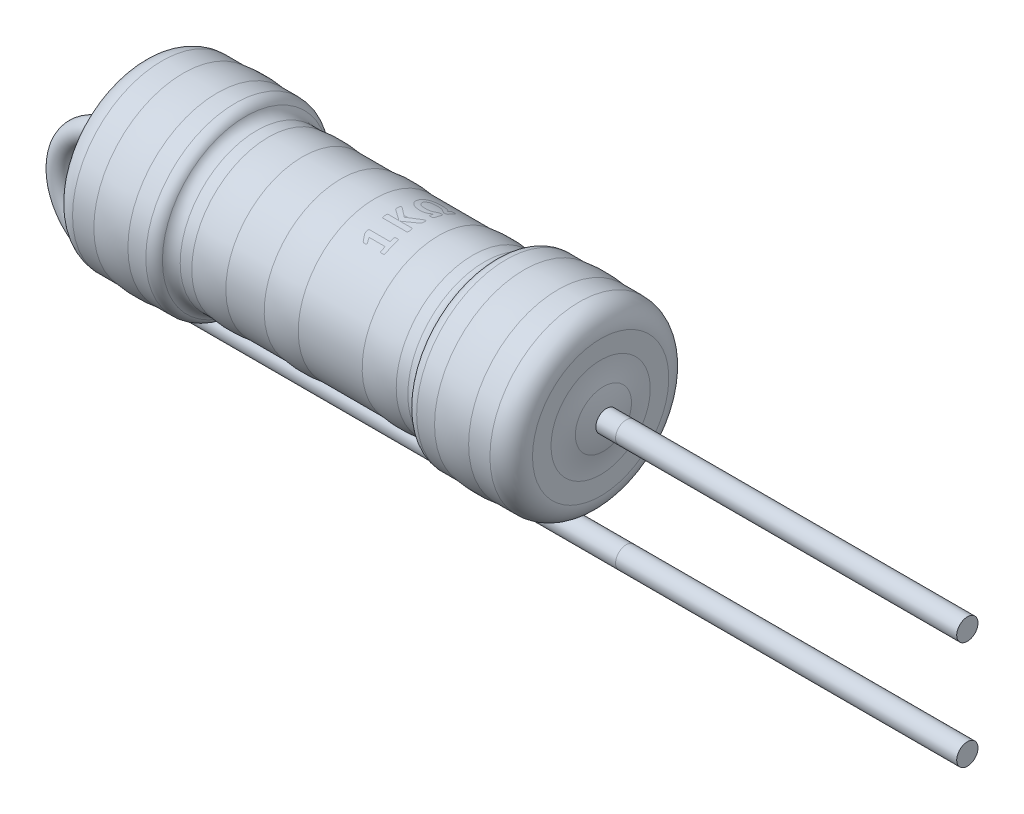
SolidWorks part; units mm, degrees
ref_plane "Front Plane" through (0, 0, 0) normal (0, 0, 1) x (1, 0, 0)
ref_plane "Top Plane" through (0, 0, 0) normal (0, 1, 0) x (1, 0, 0)
ref_plane "Right Plane" through (0, 0, 0) normal (1, 0, 0) x (0, 0, -1)
sketch "Sketch Set Wire Width" plane through (0, 0, 0) normal (0, 0, 1) x (1, 0, 0)
  line L0 (0, 0) -> (6, 0)
  line L1 (6, -2.54) -> (-6, -2.54)
  line L2 (6, 0) -> (14.0102, 0)
  line L3 (-6, 0) -> (-6, -2.54) construction
  line L4 (-6, 0) -> (-6, -2.54) construction
  line L5 (6, -2.54) -> (6, 0) construction
  line L6 (6, -2.54) -> (14.0102, -2.54)
  line L7 (14.0102, -2.54) -> (14.0102, 0) construction
  line L8 (-6, 0) -> (0, 0)
  arc A0 (-6, 0) -> (-6, -2.54) centre (-6, -1.27) ccw
  dimension "D2" = 2.54
  dimension "D3" = 30
  dimension "D1" = 12
  dimension "D4" = 6
sketch "Sketch Wire Diameter" plane through (0, 0, 0) normal (1, 0, 0) x (0, 0, -1)
  circle A0 centre (0, 0) radius 0.25
  dimension "D1" = 0.5
sweep "SET WIRE LENGTH" add profiles "Sketch Wire Diameter" path "Sketch Set Wire Width"
sketch "Sketch3" plane through (0, 0, 0) normal (0, 0, 1) x (1, 0, 0)
  line L0 (-5.4, 0) -> (5.4, 0)
  line L1 (0, 0) -> (0, 1.8) construction
  line L2 (-2.9, 1.8) -> (2.9, 1.8)
  line L3 (-5.4, 0) -> (-5.4, 1.6)
  line L4 (-4.9, 2.1) -> (-3.18, 2.1)
  line L5 (-2.9, 1.82) -> (-2.9, 1.8)
  line L6 (5.4, 0) -> (5.4, 1.6)
  line L7 (4.9, 2.1) -> (3.18, 2.1)
  line L8 (2.9, 1.82) -> (2.9, 1.8)
  arc A0 (-5.4, 1.6) -> (-4.9, 2.1) centre (-4.9, 1.6) cw
  arc A1 (5.4, 1.6) -> (4.9, 2.1) centre (4.9, 1.6) ccw
  arc A2 (-3.18, 2.1) -> (-2.9, 1.82) centre (-3.18, 1.82) cw
  arc A3 (3.18, 2.1) -> (2.9, 1.82) centre (3.18, 1.82) ccw
  dimension "D5" = 0.5
  dimension "D6" = 0.28
  dimension "D1" = 10.8
  dimension "D2" = 5.8
  dimension "D3" = 1.8
  dimension "D4" = 2.1
revolve "Revolve2" add sketch "Sketch3" angle 360 about L0
fillet "Fillet1" radius 0.3 2 edges at (2.9, 0, 1.8) (-2.9, 0, 1.8)
sketch "Sketch5" plane through (0, 0, 0) normal (0, 0, 1) x (1, 0, 0)
  line L0 (0, 0) -> (2, 0) construction
  line L1 (0, 0) -> (-0.3, 0) construction
  line L2 (-0.3, 0) -> (-2, 0) construction
  line L3 (-2, 0) -> (-4, 0) construction
  line L4 (2, 0) -> (4, 0) construction
  line L5 (-4, 0) -> (-4, 2.1) construction
  line L6 (-0.3, 0) -> (-0.3, 1.8) construction
  line L7 (-2, 0) -> (-2, 1.8) construction
  line L8 (2, 0) -> (2, 1.8) construction
  line L9 (4, 0) -> (4, 2.1) construction
  line L10 (-4, 2.1) -> (-4, 2.13) construction
  line L11 (-4.9, 2.1) -> (-3.18, 2.1) construction
  line L12 (4.9, 2.1) -> (3.18, 2.1) construction
  line L13 (-2.9, 1.8) -> (2.9, 1.8) construction
  line L14 (-2, 1.8) -> (-2, 1.83) construction
  line L17 (-4.4, 2.1) -> (-3.6, 2.1)
  line L19 (-5.4, 0) -> (5.4, 0) construction
  line L22 (-2.4, 1.8) -> (-1.6, 1.8) construction
  line L26 (-0.7, 1.8) -> (0.1, 1.8) construction
  line L30 (1.6, 1.8) -> (2.4, 1.8) construction
  line L34 (3.6, 2.1) -> (4.4, 2.1) construction
  line L36 (-0.3, 1.8) -> (-0.3, 1.83) construction
  line L37 (2, 1.8) -> (2, 1.83) construction
  line L38 (4, 2.1) -> (4, 2.13) construction
  arc A0 (-4.4, 2.1) -> (-3.6, 2.1) centre (-4, -0.5517) cw
  arc A1 (-2.4, 1.8) -> (-1.6, 1.8) centre (-2, -0.8517) cw construction
  arc A2 (-0.7, 1.8) -> (0.1, 1.8) centre (-0.3, -0.8517) cw construction
  arc A3 (1.6, 1.8) -> (2.4, 1.8) centre (2, -0.8517) cw construction
  arc A4 (3.6, 2.1) -> (4.4, 2.1) centre (4, -0.5517) cw construction
  dimension "D3" = 0.8
  dimension "D1" = 4
  dimension "D2" = 4
  dimension "D4" = 0.03
  dimension "D5" = 2
  dimension "D6" = 2
  dimension "D7" = 1.7
revolve "Band 1" add sketch "Sketch5" angle 360 about L2
sketch "Sketch8" plane through (0, 0, 0) normal (0, 0, 1) x (1, 0, 0)
  line L0 (-2.4, 1.8) -> (-1.6, 1.8) construction
  line L1 (-2.4, 1.8) -> (-1.6, 1.8)
  arc A0 (-1.6, 1.8) -> (-2.4, 1.8) centre (-2, -0.8517) ccw construction
  arc A1 (-1.6, 1.8) -> (-2.4, 1.8) centre (-2, -0.8517) ccw
revolve "Band 2" add sketch "Sketch8" angle 360 about L2
sketch "Sketch9" plane through (0, 0, 0) normal (0, 0, 1) x (1, 0, 0)
  line L0 (-0.7, 1.8) -> (0.1, 1.8) construction
  line L1 (-0.7, 1.8) -> (0.1, 1.8)
  arc A0 (0.1, 1.8) -> (-0.7, 1.8) centre (-0.3, -0.8517) ccw construction
  arc A1 (0.1, 1.8) -> (-0.7, 1.8) centre (-0.3, -0.8517) ccw
revolve "Band 3" add sketch "Sketch9" angle 360 about L2
sketch "Sketch10" plane through (0, 0, 0) normal (0, 0, 1) x (1, 0, 0)
  line L0 (1.6, 1.8) -> (2.4, 1.8) construction
  line L1 (1.6, 1.8) -> (2.4, 1.8)
  arc A0 (2.4, 1.8) -> (1.6, 1.8) centre (2, -0.8517) ccw construction
  arc A1 (2.4, 1.8) -> (1.6, 1.8) centre (2, -0.8517) ccw
revolve "Band 4" add sketch "Sketch10" angle 360 about L0
sketch "Sketch11" plane through (0, 0, 0) normal (0, 0, 1) x (1, 0, 0)
  line L0 (3.6, 2.1) -> (4.4, 2.1) construction
  line L1 (3.6, 2.1) -> (4.4, 2.1)
  arc A0 (4.4, 2.1) -> (3.6, 2.1) centre (4, -0.5517) ccw construction
  arc A1 (4.4, 2.1) -> (3.6, 2.1) centre (4, -0.5517) ccw
revolve "Band 5" add sketch "Sketch11" angle 360 about L4
sketch "Sketch12" plane through (0, 0, 0) normal (0, 0, 1) x (1, 0, 0)
  line L0 (-5.35, 0) -> (5.35, 0) construction
  line L1 (-5.35, 1) -> (-5.35, 0)
  line L2 (5.35, 1) -> (5.35, 0)
  line L3 (-5.35, 0) -> (-5.55, 0)
  line L4 (5.35, 0) -> (5.55, 0)
  arc A0 (-5.35, 1) -> (-5.55, 0) centre (-2.95, 0) ccw
  arc A1 (5.35, 1) -> (5.55, 0) centre (2.95, 0) cw
  dimension "D3" = 0.2
  dimension "D4" = 2.6
  dimension "D1" = 10.7
  dimension "D2" = 1
revolve "Revolve10" add sketch "Sketch12" angle 360 about L0
fillet "Fillet2" radius 2 2 edges at (5.4, 0, 0.8703) (-5.4, 0, -0.8703)
ref_plane "Plane2" through (0, 3, 0) normal (0, 1, 0) x (1, 0, 0)
sketch "Sketch13" plane through (0, 3, 0) normal (0, 1, 0) x (1, 0, 0)
  line L0 (0, 0) -> (1.15, 0) construction
  line L1 (1.15, 1.75) -> (1.15, -1.75) construction
  text T0 "1KΩ" font "Calibri" height 0.6
  dimension "D1" = 3.5
  dimension "D2" = 1.15
wrap "Wrap1" sketch "Sketch13" wrap type scribe source sketch "Sketch13" face at (0.1, 1.8, 0)
